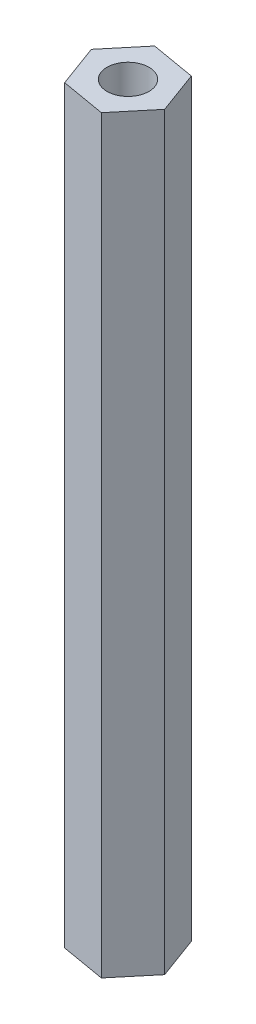
SolidWorks part; units mm, degrees
ref_plane "Front Plane" through (0, 0, 0) normal (0, 0, 1) x (1, 0, 0)
ref_plane "Top Plane" through (0, 0, 0) normal (0, 1, 0) x (1, 0, 0)
ref_plane "Right Plane" through (0, 0, 0) normal (1, 0, 0) x (0, 0, -1)
sketch "Sketch1" plane through (0, 0, 0) normal (0, 1, 0) x (1, 0, 0)
  line L0 (1.0373, -2.815) -> (2.9565, -0.5091)
  line L1 (2.9565, -0.5091) -> (1.9192, 2.3058)
  line L2 (1.9192, 2.3058) -> (-1.0373, 2.815)
  line L3 (-1.0373, 2.815) -> (-2.9565, 0.5091)
  line L4 (-2.9565, 0.5091) -> (-1.9192, -2.3058)
  line L5 (-1.9192, -2.3058) -> (1.0373, -2.815)
  circle A0 centre (0, 0) radius 1.4
extrude "Boss-Extrude1" add sketch "Sketch1" along normal blind 50
